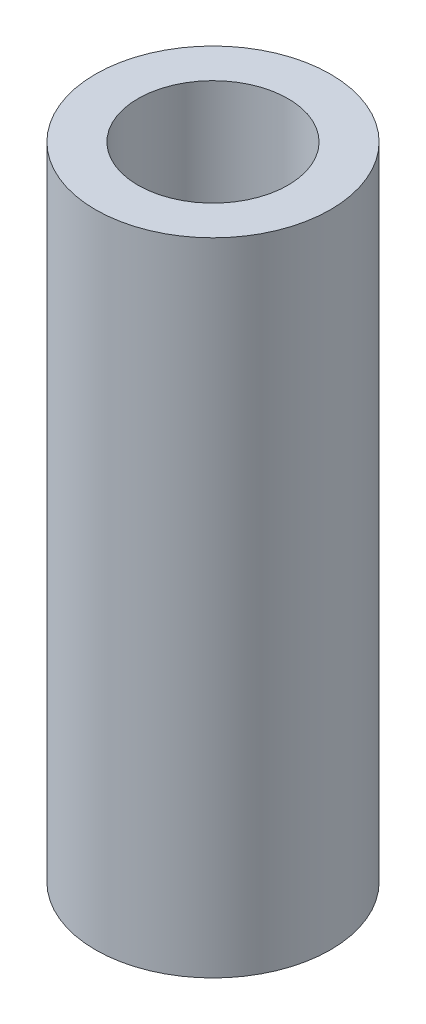
SolidWorks part; units mm, degrees
ref_plane "Front Plane" through (0, 0, 0) normal (0, 0, 1) x (1, 0, 0)
ref_plane "Top Plane" through (0, 0, 0) normal (0, 1, 0) x (1, 0, 0)
ref_plane "Right Plane" through (0, 0, 0) normal (1, 0, 0) x (0, 0, -1)
sketch "Sketch1" plane through (0, 0, 0) normal (0, 1, 0) x (1, 0, 0)
  circle A0 centre (0, 0) radius 25
  dimension "SLEEVE_OD" = 50
extrude "Boss-Extrude1" add sketch "Sketch1" along normal blind 136.4317
sketch "Sketch2" plane through (0, 0, 0) normal (0, 1, 0) x (1, 0, 0)
  circle A0 centre (0, 0) radius 15.971
  dimension "BORE_D" = 31.942
extrude "Cut-Extrude1" cut sketch "Sketch2" along normal through all
chamfer "Chamfer1" distance 3.7717 angle 60 rebuild error yes
